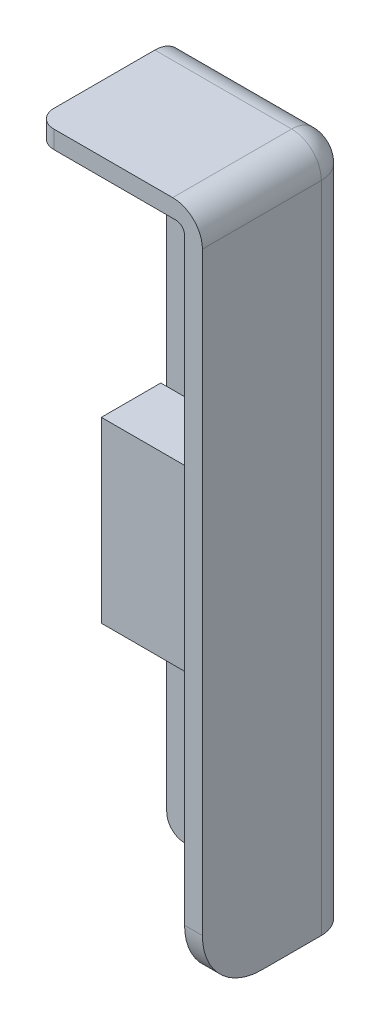
SolidWorks part; units mm, degrees
material "ABS"
ref_plane "Front" through (0, 0, 0) normal (0, 0, 1) x (1, 0, 0)
ref_plane "Top" through (0, 0, 0) normal (0, 1, 0) x (1, 0, 0)
ref_plane "Right" through (0, 0, 0) normal (1, 0, 0) x (0, 0, -1)
sketch "Sketch1" plane through (0, 0, 0) normal (1, 0, 0) x (0, 0, -1)
  line L1 (-12.5, 57.5) -> (12.5, 57.5)
  line L2 (-12.5, 57.5) -> (-12.5, -57.5)
  line L3 (-12.5, -57.5) -> (12.5, -57.5)
  line L4 (12.5, 57.5) -> (12.5, -57.5)
  line L5 (-12.5, 57.5) -> (12.5, -57.5) construction
  line L6 (-12.5, -57.5) -> (12.5, 57.5) construction
  point P0 (0, 0)
  dimension "D1" = 25
  dimension "D2" = 115
extrude "Boss-Extrude1" add sketch "Sketch1" along normal mid plane 28
sketch "Sketch3" plane through (-14, 0, 0) normal (1, 0, 0) x (0, 0, -1)
  line L1 (-12.5, -57.5) -> (9.5, -57.5)
  line L2 (-12.5, -57.5) -> (-12.5, 54.5)
  line L3 (-12.5, 54.5) -> (9.5, 54.5)
  line L4 (9.5, -57.5) -> (9.5, 54.5)
  dimension "D1" = 22
  dimension "D2" = 112
extrude "Cut-Extrude1" cut sketch "Sketch3" along normal offset from surface (25 mm away) 3 up to face at (14, 0, 0)
sketch "Sketch4" plane through (11, 0, 0) normal (-1, 0, 0) x (0, 0, 1)
  line L0 (12.5, -1.5) -> (-9.5, -1.5) construction
  line L1 (12.5, 54.5) -> (12.5, -57.5) construction
  line L2 (-9.5, -57.5) -> (-9.5, 54.5) construction
  line L4 (-3.5, 13.5) -> (6.5, 13.5)
  line L5 (-3.5, 13.5) -> (-3.5, -16.5)
  line L6 (-3.5, -16.5) -> (6.5, -16.5)
  line L7 (6.5, 13.5) -> (6.5, -16.5)
  line L8 (-3.5, 13.5) -> (6.5, -16.5) construction
  line L9 (-3.5, -16.5) -> (6.5, 13.5) construction
  point P6 (1.5, -1.5)
  dimension "D1" = 30
  dimension "D2" = 10
extrude "Boss-Extrude2" add sketch "Sketch4" along normal blind 20
hole_wizard "#2 Clearance Hole1" positions "Sketch5" profile "Sketch6" hole size "#2" standard "ANSI Inch"
sketch "Sketch5" plane through (-9, 0, 0) normal (-1, 0, 0) x (0, 0, 1)
  line L0 (1.5, 13.5) -> (1.5, -16.5) construction
  line L1 (6.5, 13.5) -> (-3.5, 13.5) construction
  line L2 (-3.5, -16.5) -> (6.5, -16.5) construction
  line L4 (-3.5, -1.5) -> (6.5, -1.5) construction
  line L5 (-3.5, 13.5) -> (-3.5, -16.5) construction
  line L6 (6.5, -16.5) -> (6.5, 13.5) construction
  point P0 (1.5, 8.5)
  point P2 (1.5, -11.5)
  dimension "D1" = 10
  dimension "D2" = 10
sketch "Sketch6" plane through (-9, 8.5, 1.5) normal (0, 1, 0) x (0, 0, 1)
  line L0 (0, 0) -> (0, 7.0292)
  line L1 (0, 7.0292) -> (1.1303, 6.35)
  line L2 (1.1303, 6.35) -> (1.1303, 0)
  line L5 (1.1303, 0) -> (0, 0)
  line L10 (0, 7.0292) -> (-1.1303, 6.35) construction
  line L11 (0, -6.35) -> (0, 107.95) construction
  dimension "Hole Dia." = 2.2606
  dimension "Hole Depth" = 6.35
  dimension "Drill Angle" = 118
fillet "Fillet1" radius 1.5 3 edges at (11, -1.5, -9.5) (-1.5, 54.5, -9.5) (11, 54.5, 1.5)
fillet "Fillet3" radius 5 3 edges at (0, 57.5, -12.5) (14, 57.5, 0) (14, 0, -12.5)
fillet "Fillet4" radius 10 1 edges at (12.5, -57.5, 12.5)
fillet "Fillet5" radius 3 2 edges at (-14, -57.5, -11) (-14, 56, 12.5)
fillet "Fillet6" radius 3 4 edges at (11, 13.5, 1.5) (11, -1.5, -3.5) (11, -16.5, 1.5) (11, -1.5, 6.5)
sketch "Sketch7" plane through (14, 0, 0) normal (1, 0, 0) x (0, 0, -1)
  circle A0 centre (-1.5006, -43.0001) radius 3.7 construction
  arc A1 (-3.6164, -46.0355) -> (-4.1645, -40.4322) centre (-1.5006, -43.0001) ccw construction
  circle A2 centre (-1.5006, -43.0001) radius 2.7
  dimension "D1" = 1
extrude "Boss-Extrude3" add sketch "Sketch7" against normal blind 8
fillet "Fillet7" radius 1 2 edges at (11, -43.0001, -1.1994) (6, -43.0001, -1.1994)
move or copy body "Body-Move/Copy1" [suppressed] bodies to move or copy 105
